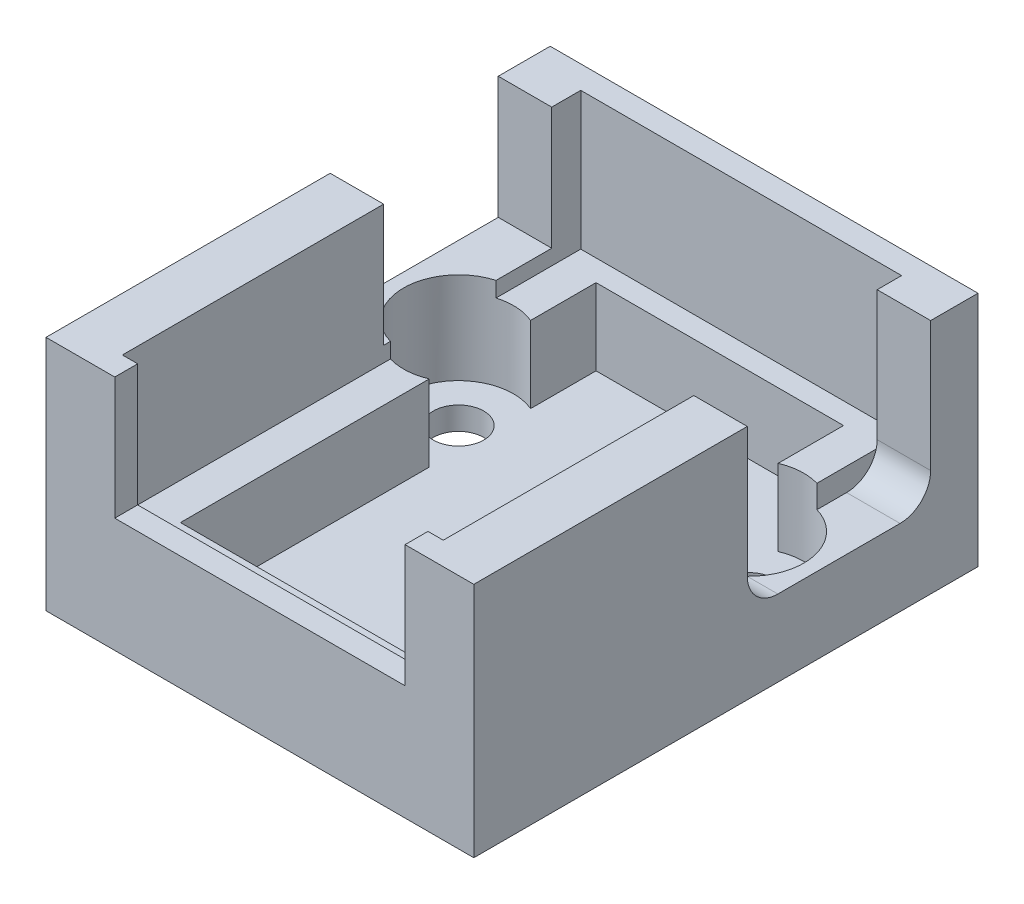
SolidWorks part; units mm, degrees
ref_plane "Płaszczyzna przednia" through (0, 0, 0) normal (0, 0, 1) x (1, 0, 0)
ref_plane "Płaszczyzna górna" through (0, 0, 0) normal (0, 1, 0) x (1, 0, 0)
ref_plane "Płaszczyzna prawa" through (0, 0, 0) normal (1, 0, 0) x (0, 0, -1)
sketch "Szkic1" plane through (0, 0, 0) normal (0, 1, 0) x (1, 0, 0)
  line L1 (-14, -16.5) -> (14, -16.5)
  line L2 (-14, -16.5) -> (-14, 16.5)
  line L3 (-14, 16.5) -> (14, 16.5)
  line L4 (14, -16.5) -> (14, 16.5)
  line L5 (-14, -16.5) -> (14, 16.5) construction
  line L6 (-14, 16.5) -> (14, -16.5) construction
  point P0 (0, 0)
  dimension "D1" = 28
  dimension "D2" = 33
extrude "Dodanie-wyciągnięcie1" add sketch "Szkic1" along normal blind 1.5
sketch "Szkic2" plane through (0, 1.5, 0) normal (0, 1, 0) x (1, 0, 0)
  line L0 (-14, 16.5) -> (14, 16.5)
  line L1 (14, 16.5) -> (14, -16.5)
  line L2 (14, -16.5) -> (-14, -16.5)
  line L3 (-14, -16.5) -> (-14, 16.5)
  line L5 (-10.5, -15) -> (10.5, -15)
  line L6 (-10.5, -15) -> (-10.5, 15)
  line L7 (-10.5, 15) -> (10.5, 15)
  line L8 (10.5, -15) -> (10.5, 15)
  line L9 (-10.5, -15) -> (10.5, 15) construction
  line L10 (-10.5, 15) -> (10.5, -15) construction
  point P4 (0, 0)
  dimension "D1" = 1.5
  dimension "D2" = 3.5
  dimension "D3" = 3.5
  dimension "D4" = 1.5
extrude "Dodanie-wyciągnięcie2" add sketch "Szkic2" along normal blind 14
sketch "Szkic7" plane through (0, 1.5, 0) normal (0, 1, 0) x (1, 0, 0)
  line L1 (-10.5, -15) -> (10.5, -15)
  line L2 (-10.5, -15) -> (-10.5, 15)
  line L3 (-10.5, 15) -> (10.5, 15)
  line L4 (10.5, -15) -> (10.5, 15)
  line L5 (-10.5, -15) -> (10.5, 15) construction
  line L6 (-10.5, 15) -> (10.5, -15) construction
  line L7 (-8.1, -13.6) -> (8.1, -13.6)
  line L8 (-8.1, -13.6) -> (-8.1, 13.6)
  line L9 (-8.1, 13.6) -> (8.1, 13.6)
  line L10 (8.1, -13.6) -> (8.1, 13.6)
  line L11 (-8.1, -13.6) -> (8.1, 13.6) construction
  line L12 (-8.1, 13.6) -> (8.1, -13.6) construction
  point P0 (0, 0)
  point P7 (0, 0)
  dimension "D1" = 1.4
  dimension "D2" = 2.4
extrude "Dodanie-wyciągnięcie4" add sketch "Szkic7" along normal blind 5
sketch "Szkic3" plane through (14, 0, 0) normal (1, 0, 0) x (0, 0, -1)
  line L0 (16.5, 0) -> (16.5, 5) construction
  line L1 (16.5, 15.5) -> (16.5, 0) construction
  line L2 (16.5, 5) -> (13.4, 5) construction
  line L3 (13.4, 5) -> (1.4, 5)
  line L4 (1.4, 5) -> (1.4, 15.5)
  line L5 (-16.5, 15.5) -> (16.5, 15.5) construction
  line L6 (1.4, 15.5) -> (13.4, 15.5)
  line L7 (13.4, 15.5) -> (13.4, 5)
  dimension "D1" = 3.1
  dimension "D2" = 12
  dimension "D3" = 5
extrude "Wytnij-wyciągnięcie1" cut sketch "Szkic3" against normal up to surface (3.5 mm away) contours L3 L4 L6 L7 up to face at (10.5, 11, 0)
sketch "Szkic4" plane through (0, 0, 16.5) normal (0, 0, 1) x (1, 0, 0)
  line L0 (14, 0) -> (14, 7.5) construction
  line L1 (-14, 0) -> (14, 0) construction
  line L2 (14, 15.5) -> (14, 0) construction
  line L3 (14, 7.5) -> (9.5, 7.5) construction
  line L4 (9.5, 7.5) -> (9.5, 15.5)
  line L5 (-14, 15.5) -> (14, 15.5) construction
  line L6 (9.5, 15.5) -> (-9.5, 15.5)
  line L7 (-9.5, 15.5) -> (-9.5, 7.5)
  line L8 (-9.5, 7.5) -> (9.5, 7.5)
  line L9 (-14, 15.5) -> (-14, 0) construction
  dimension "D1" = 4.5
  dimension "D2" = 4.5
  dimension "D3" = 7.5
extrude "Wytnij-wyciągnięcie2" cut sketch "Szkic4" against normal up to surface (1.5 mm away) up to face at (0, 11, 15)
sketch "Szkic5" plane through (-14, 0, 0) normal (-1, 0, 0) x (0, 0, 1)
  line L0 (-16.5, 0) -> (-16.5, 7.5) construction
  line L1 (-16.5, 0) -> (16.5, 0) construction
  line L2 (-16.5, 15.5) -> (-16.5, 0) construction
  line L3 (-16.5, 7.5) -> (-13.1, 7.5) construction
  line L4 (-13.1, 7.5) -> (-13.1, 15.5)
  line L5 (-13.1, 15.5) -> (-2.1, 15.5)
  line L6 (-2.1, 15.5) -> (-2.1, 7.5)
  line L7 (-2.1, 7.5) -> (-13.1, 7.5)
  line L8 (-16.5, 15.5) -> (16.5, 15.5) construction
  dimension "D1" = 3.4
  dimension "D2" = 7.5
  dimension "D3" = 11
extrude "Wytnij-wyciągnięcie3" cut sketch "Szkic5" against normal up to surface (3.5 mm away) up to face at (-10.5, 11, 0)
sketch "Szkic8" plane through (0, 0, 0) normal (0, -1, 0) x (1, 0, 0)
  line L0 (0, 0) -> (0, -6) construction
  line L1 (-9.5, -6) -> (9.5, -6) construction
  circle A0 centre (9.5, -6) radius 1.65
  circle A1 centre (-9.5, -6) radius 1.65
  point P6 (0, -6)
  dimension "D3" = 3.3
  dimension "D1" = 6
  dimension "D2" = 19
extrude "Wytnij-wyciągnięcie4" cut sketch "Szkic8" against normal through all
sketch "Szkic9" plane through (0, 0, 0) normal (0, -1, 0) x (1, 0, 0)
  line L0 (0, 0) -> (0, -4.7269) construction
  circle A0 centre (-9.5, -6) radius 3.6
  circle A1 centre (9.5, -6) radius 3.6
  dimension "D1" = 7.2
extrude "Wytnij-wyciągnięcie8" cut sketch "Szkic9" against normal through all from surface starting at face at (0, 1.5, -3)
fillet "Zaokrąglenie1" radius 2 2 edges at (12.25, 5, -1.4) (12.25, 5, -13.4)
